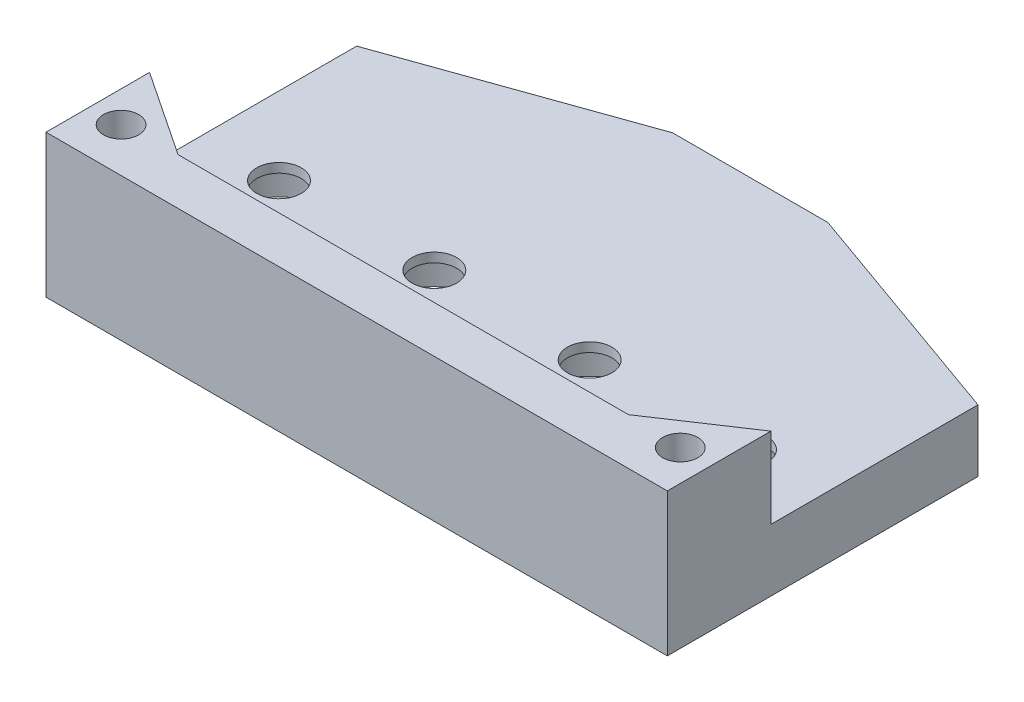
SolidWorks part; units mm, degrees
ref_plane "Front Plane" through (0, 0, 0) normal (0, 0, 1) x (1, 0, 0)
ref_plane "Top Plane" through (0, 0, 0) normal (0, 1, 0) x (1, 0, 0)
ref_plane "Right Plane" through (0, 0, 0) normal (1, 0, 0) x (0, 0, -1)
sketch "Sketch2" plane through (0, 0, 0) normal (0, 1, 0) x (1, 0, 0)
  line L0 (0, 0) -> (0, 30)
  line L1 (0, 30) -> (22.5, 38)
  line L2 (22.5, 38) -> (37.5, 38)
  line L3 (37.5, 38) -> (60, 30)
  line L4 (60, 30) -> (60, 0)
  line L5 (60, 0) -> (0, 0)
  line L6 (22.5, 15) -> (37.5, 15) construction
  line L7 (30, 38) -> (30, 0) construction
  circle A0 centre (7.5, 15) radius 2.15
  circle A1 centre (22.5, 15) radius 2.15
  circle A2 centre (37.5, 15) radius 2.15
  circle A3 centre (52.5, 15) radius 2.15
  point P17 (30, 15)
  point P18 (0, 0)
  point P19 (60, 15)
  dimension "D5" = 4.3
  dimension "D7" = 15
  dimension "D8" = 15
  dimension "D9" = 15
  dimension "D1" = 60
  dimension "D2" = 30
  dimension "D3" = 15
  dimension "D4" = 8
extrude "Boss-Extrude1" add sketch "Sketch2" along normal blind 6
sketch "Sketch3" plane through (0, 6, 0) normal (0, 1, 0) x (1, 0, 0)
  line L0 (0, 0) -> (0, 10)
  line L1 (0, 30) -> (0, 0) construction
  line L2 (0, 10) -> (15, 0)
  line L3 (0, 0) -> (60, 0) construction
  line L4 (15, 0) -> (0, 0)
  line L5 (60, 0) -> (60, 10)
  line L6 (60, 0) -> (60, 30) construction
  line L7 (60, 10) -> (45, 0)
  line L8 (45, 0) -> (60, 0)
  line L9 (51.75, 4.5) -> (8.25, 4.5)
  line M8 (0, 0) -> (60, 0)
  line M9 (60, 0) -> (60, 30)
  line M13 (0, 30) -> (0, 0)
  dimension "D1" = 15
  dimension "D2" = 10
  dimension "D3" = 4.5
extrude "Boss-Extrude2" add sketch "Sketch3" along normal blind 7.8 contours L2 M13 M8 | L7 L9 L2 M8 | L7 M9 M8 region at (5, 6, -3.3333) region at (30, 6, -2.3878) region at (55, 6, -3.3333)
sketch "Sketch4" plane through (0, 13.8, 0) normal (0, 1, 0) x (1, 0, 0)
  line L0 (0, 0) -> (60, 0) construction
  line L1 (0, 10) -> (0, 0) construction
  line L2 (60, 0) -> (60, 10) construction
  circle A0 centre (3, 4.25) radius 1.7
  circle A1 centre (57, 4.25) radius 1.7
  dimension "D1" = 3.4
  dimension "D2" = 4.25
  dimension "D3" = 3
  dimension "D4" = 3
extrude "Cut-Extrude1" cut sketch "Sketch4" against normal through all
sketch "Sketch5" plane through (0, 0, 0) normal (0, 1, 0) x (1, 0, 0)
  circle A0 centre (7.5, 15) radius 6.55
  circle A1 centre (22.5, 15) radius 6.55
  circle A2 centre (37.5, 15) radius 6.55
  circle A3 centre (52.5, 15) radius 6.55
  dimension "D1" = 13.1
extrude "Cut-Extrude2" cut sketch "Sketch5" along normal blind 5.1
